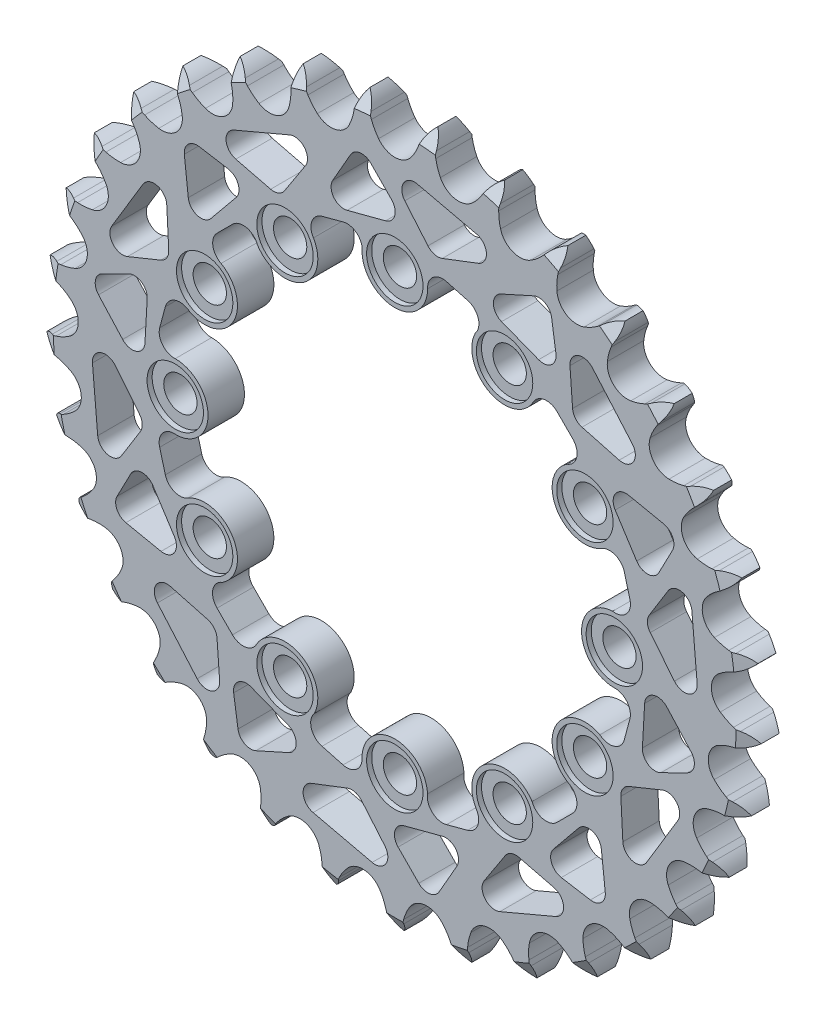
SolidWorks part; units mm, degrees
material "7075-T6 (SN)"
ref_plane "Front Plane" through (0, 0, 0) normal (0, 0, 1) x (1, 0, 0)
ref_plane "Top Plane" through (0, 0, 0) normal (0, 1, 0) x (1, 0, 0)
ref_plane "Right Plane" through (0, 0, 0) normal (1, 0, 0) x (0, 0, -1)
sketch "Work Sketch" plane through (0, 0, 0) normal (0, 0, 1) x (1, 0, 0)
  line L0 (0, 0) -> (0, 160.4542) construction
  line L1 (-112.0919, 66.8027) -> (87.2579, 66.8027) construction
  line L2 (5.0834, 120.8822) -> (5.0834, 112.9699) construction
  line L3 (-12.8497, 70.6081) -> (16.7256, 70.6081) construction
  line L4 (5.0834, 70.6081) -> (-6.0658, 62.2619) construction
  line L5 (5.0834, 70.6081) -> (-4.6352, 66.9715) construction
  line L6 (-4.6352, 66.9715) -> (-6.998, 73.2861)
  line L7 (-11.5114, 65.7464) -> (-7.1525, 65.7464) construction
  line L8 (-11.0622, 124.7602) -> (-11.0622, 110.2345) construction
  line L9 (0, 0) -> (-4.0639, 42.5596) construction
  circle A0 centre (0, 0) radius 66.8027
  circle A1 centre (0, 66.8027) radius 4.0088
  arc A2 (-4.6352, 66.9715) -> (-3.2092, 64.4003) centre (5.0609, 70.6677) ccw
  circle A3 centre (-11.0622, 65.7464) radius 6.4488
  point P23 (-3.2092, 64.4003)
  dimension "D1" = 133.6054
  dimension "D8" = 10.3767
  dimension "D2" = 8.0177
  dimension "D3" = 5.0834
  dimension "D4" = 3.8054
  dimension "D5" = 36.818
  dimension "D6" = 16.303
  dimension "D7" = 10.3767
  dimension "D9" = 1.0563
  dimension "D10" = 11.0622
  dimension "D11" = 5.455
sketch "Teeth Sketch" plane through (0, 0, 0) normal (0, 0, 1) x (1, 0, 0)
  line L0 (5.0224, 68.0064) -> (4.6352, 66.9715)
  line L1 (-8.8439, 92.6176) -> (-5.6513, 59.1829) construction
  line L2 (0, 0) -> (-12.8498, 132.1321) construction
  line L3 (7.9387, 67.7279) -> (8.123, 66.6385)
  line L4 (19011.2087, -199094.3845) -> (-19015.2726, 199136.9441) construction
  line L5 (0, 146.3285) -> (0, 56.9858) construction
  line L6 (17.8019, 65.8269) -> (17.2258, 64.8841)
  line L7 (0, -200000) -> (0, 200160.4542) construction
  line L8 (20.6128, 65.0016) -> (20.5877, 63.897)
  line L9 (-4.6352, 66.9715) -> (-6.998, 73.2861) construction
  line L10 (43.2949, 52.6844) -> (42.861, 51.6682)
  line L11 (-5.0224, 68.0064) -> (-4.6352, 66.9715)
  line L12 (29.938, 61.2683) -> (29.1939, 60.4515)
  line L13 (32.5419, 59.9259) -> (32.3082, 58.846)
  line L14 (40.9921, 54.4953) -> (40.1069, 53.8341)
  line L15 (50.5647, 45.7527) -> (49.5703, 45.271)
  line L16 (52.4831, 43.5387) -> (51.8648, 42.623)
  line L17 (58.3096, 35.3565) -> (57.2421, 35.0716)
  line L18 (59.7744, 32.8194) -> (58.9939, 32.0373)
  line L19 (63.9472, 23.6824) -> (62.845, 23.6047)
  line L20 (64.9053, 20.9139) -> (63.9909, 20.2936)
  line L21 (67.2735, 11.1523) -> (66.1765, 11.2846)
  line L22 (67.6904, 8.2526) -> (66.6751, 7.8165)
  line L23 (68.1683, -1.7808) -> (67.1162, -1.4433)
  line L24 (68.0289, -4.7071) -> (66.9495, -4.9431)
  line L25 (66.5994, -14.6496) -> (65.6302, -14.119)
  line L26 (65.9088, -17.4966) -> (64.8042, -17.524)
  line L27 (62.6234, -26.9889) -> (61.7722, -26.2845)
  line L28 (61.4065, -29.6537) -> (60.3166, -29.4716)
  line L29 (56.3841, -38.3527) -> (55.6815, -37.4999)
  line L30 (54.6848, -40.739) -> (53.6491, -40.354)
  line L31 (48.1068, -48.3304) -> (47.5783, -47.3601)
  line L32 (45.9866, -50.352) -> (45.0425, -49.7779)
  line L33 (38.0909, -56.5613) -> (37.7556, -55.5085)
  line L34 (35.6264, -58.1451) -> (34.808, -57.4027)
  line L35 (26.6983, -62.7479) -> (26.5682, -61.6506)
  line L36 (23.9786, -63.8367) -> (23.3155, -62.9529)
  line L37 (14.3407, -66.6666) -> (14.4207, -65.5646)
  line L38 (11.4641, -67.221) -> (10.9802, -66.2277)
  line L39 (1.4648, -68.1759) -> (1.7519, -67.1089)
  line L40 (-1.4648, -68.1759) -> (-1.7519, -67.1089)
  line L41 (-11.4641, -67.221) -> (-10.9802, -66.2277)
  line L42 (-14.3407, -66.6666) -> (-14.4207, -65.5646)
  line L43 (-23.9786, -63.8367) -> (-23.3155, -62.9529)
  line L44 (-26.6983, -62.7479) -> (-26.5682, -61.6506)
  line L45 (-35.6264, -58.1451) -> (-34.808, -57.4027)
  line L46 (-38.0909, -56.5613) -> (-37.7556, -55.5085)
  line L47 (-45.9866, -50.352) -> (-45.0425, -49.7779)
  line L48 (-48.1068, -48.3304) -> (-47.5783, -47.3601)
  line L49 (-54.6848, -40.739) -> (-53.6491, -40.354)
  line L50 (-56.3841, -38.3527) -> (-55.6815, -37.4999)
  line L51 (-61.4065, -29.6537) -> (-60.3166, -29.4716)
  line L52 (-62.6234, -26.9889) -> (-61.7722, -26.2845)
  line L53 (-65.9088, -17.4966) -> (-64.8042, -17.524)
  line L54 (-66.5994, -14.6496) -> (-65.6302, -14.119)
  line L55 (-68.0289, -4.7071) -> (-66.9495, -4.9431)
  line L56 (-68.1683, -1.7808) -> (-67.1162, -1.4433)
  line L57 (-67.6904, 8.2526) -> (-66.6751, 7.8165)
  line L58 (-67.2735, 11.1523) -> (-66.1765, 11.2846)
  line L59 (-64.9053, 20.9139) -> (-63.9909, 20.2936)
  line L60 (-63.9472, 23.6824) -> (-62.845, 23.6047)
  line L61 (-59.7744, 32.8194) -> (-58.9939, 32.0373)
  line L62 (-58.3096, 35.3565) -> (-57.2421, 35.0716)
  line L63 (-52.4831, 43.5387) -> (-51.8648, 42.623)
  line L64 (-50.5647, 45.7527) -> (-49.5703, 45.271)
  line L65 (-43.2949, 52.6844) -> (-42.861, 51.6682)
  line L66 (-40.9921, 54.4953) -> (-40.1069, 53.8341)
  line L67 (-32.5419, 59.9259) -> (-32.3082, 58.846)
  line L68 (-29.938, 61.2683) -> (-29.1939, 60.4515)
  line L69 (-20.6128, 65.0016) -> (-20.5877, 63.897)
  line L70 (-17.8019, 65.8269) -> (-17.2258, 64.8841)
  line L71 (-7.9387, 67.7279) -> (-8.123, 66.6385)
  arc A0 (-6.8704, 70.647) -> (-5.0224, 68.0064) centre (-11.0622, 65.7464) cw
  circle A1 centre (-11.0622, 65.7464) radius 6.4488 construction
  arc A2 (-3.2092, 64.4003) -> (-4.6352, 66.9715) centre (5.0609, 70.6677) cw
  arc A3 (-4.6352, 66.9715) -> (-3.2092, 64.4003) centre (5.0609, 70.6677) ccw construction
  circle A4 centre (0, 66.8027) radius 4.0088 construction
  arc A5 (-3.2092, 64.4003) -> (3.2092, 64.4003) centre (0, 66.8027) ccw
  arc A6 (3.2092, 64.4003) -> (4.6352, 66.9715) centre (-5.0609, 70.6677) ccw
  arc A7 (6.8704, 70.647) -> (5.0224, 68.0064) centre (11.0622, 65.7464) ccw
  arc A8 (6.6238, 70.6705) -> (7.9387, 67.7279) centre (1.5803, 66.6518) cw
  arc A9 (9.0366, 63.8438) -> (8.123, 66.6385) centre (18.3434, 68.4328) cw
  arc A10 (9.0366, 63.8438) -> (15.3391, 62.6291) centre (12.6425, 65.5955) ccw
  arc A11 (15.3391, 62.6291) -> (17.2258, 64.8841) centre (8.4044, 70.3484) ccw
  arc A12 (20.1163, 68.0701) -> (17.8019, 65.8269) centre (23.3049, 62.4647) ccw
  arc A13 (19.8786, 68.1399) -> (20.6128, 65.0016) centre (14.1657, 65.1482) cw
  arc A14 (20.9558, 60.9799) -> (20.5877, 63.897) centre (30.9629, 63.7246) cw
  arc A15 (20.9558, 60.9799) -> (26.9145, 58.5944) centre (24.8281, 62.0175) ccw
  arc A16 (26.9145, 58.5944) -> (29.1939, 60.4515) centre (21.5661, 67.4865) ccw
  arc A17 (32.6351, 63.0329) -> (29.938, 61.2683) centre (34.7052, 56.9254) ccw
  arc A18 (32.4149, 63.1465) -> (32.5419, 59.9259) centre (26.2391, 61.29) cw
  arc A19 (32.1176, 55.912) -> (32.3082, 58.846) centre (42.4634, 56.7133) cw
  arc A20 (32.1176, 55.912) -> (37.5172, 52.4419) centre (36.1163, 56.198) ccw
  arc A21 (37.5172, 52.4419) -> (40.1069, 53.8341) centre (33.9483, 62.1856) ccw
  arc A22 (43.9744, 55.7176) -> (40.9921, 54.4953) centre (44.8513, 49.3287) ccw
  arc A23 (43.7796, 55.8708) -> (43.2949, 52.6844) centre (37.3641, 55.2167) cw
  arc A24 (42.1187, 48.8233) -> (42.861, 51.6682) centre (52.429, 47.6521) cw
  arc A25 (42.1187, 48.8233) -> (46.7639, 44.3941) centre (46.0991, 48.3474) ccw
  arc A26 (46.7639, 44.3941) -> (49.5703, 45.271) centre (45.1035, 54.637) ccw
  arc A27 (53.7244, 46.3885) -> (50.5647, 45.7527) centre (53.3763, 39.9491) ccw
  arc A28 (53.5621, 46.5757) -> (52.4831, 43.5387) centre (47.1387, 47.1476) cw
  arc A29 (50.5974, 39.97) -> (51.8648, 42.623) centre (60.4998, 36.8687) cw
  arc A30 (50.5974, 39.97) -> (54.3205, 34.7417) centre (54.4159, 38.7494) ccw
  arc A31 (54.3205, 34.7417) -> (57.2421, 35.0716) centre (54.6285, 45.1138) ccw
  arc A32 (61.5326, 35.3828) -> (58.3096, 35.3565) centre (59.9721, 29.1257) ccw
  arc A33 (61.4087, 35.5974) -> (59.7744, 32.8194) centre (55.2096, 37.3746) cw
  arc A34 (57.2474, 29.6721) -> (58.9939, 32.0373) centre (66.384, 24.7528) cw
  arc A35 (57.2474, 29.6721) -> (59.9137, 23.8336) centre (60.7659, 27.7508) ccw
  arc A36 (59.9137, 23.8336) -> (62.845, 23.6047) centre (62.1792, 33.96) ccw
  arc A37 (67.1168, 23.0983) -> (63.9472, 23.6824) centre (64.4004, 17.2495) ccw
  arc A38 (67.0358, 23.3324) -> (64.9053, 20.9139) centre (61.2851, 26.2507) cw
  arc A39 (61.8283, 18.3017) -> (63.9909, 20.2936) centre (69.8688, 11.7422) cw
  arc A40 (61.8283, 18.3017) -> (63.3416, 12.0642) centre (64.9196, 15.7493) ccw
  arc A41 (63.3416, 12.0642) -> (66.1765, 11.2846) centre (67.4825, 21.5788) ccw
  arc A42 (70.2753, 9.9789) -> (67.2735, 11.1523) centre (66.5011, 4.7499) ccw
  arc A43 (70.2401, 10.2242) -> (67.6904, 8.2526) centre (65.1456, 14.178) cw
  arc A44 (64.1746, 6.2699) -> (66.6751, 7.8165) centre (70.8284, -1.6927) cw
  arc A45 (64.1746, 6.2699) -> (64.48, -0.1413) centre (66.727, 3.1786) ccw
  arc A46 (64.48, -0.1413) -> (67.1162, -1.4433) centre (70.3468, 8.4177) ccw
  arc A47 (70.8939, -3.5011) -> (68.1683, -1.7808) centre (66.1983, -7.9213) ccw
  arc A48 (70.9057, -3.2536) -> (68.0289, -4.7071) centre (66.6515, 1.5929) cw
  arc A49 (64.2015, -5.9885) -> (66.9495, -4.9431) centre (69.2281, -15.0665) cw
  arc A50 (64.2015, -5.9885) -> (63.2881, -12.3417) centre (66.1227, -9.507) ccw
  arc A51 (63.2881, -12.3417) -> (65.6302, -14.119) centre (70.6686, -5.0476) ccw
  arc A52 (68.9501, -16.8546) -> (66.5994, -14.6496) centre (63.5029, -20.3063) ccw
  arc A53 (69.0085, -16.6138) -> (65.9088, -17.4966) centre (65.7485, -11.0498) cw
  arc A54 (61.908, -18.0305) -> (64.8042, -17.524) centre (65.1257, -27.8957) cw
  arc A55 (61.908, -18.0305) -> (59.8087, -24.096) centre (63.1286, -21.849) ccw
  arc A56 (59.8087, -24.096) -> (61.7722, -26.2845) centre (68.4363, -18.3305) ccw
  arc A57 (64.5144, -29.5989) -> (62.6234, -26.9889) centre (58.5123, -31.9573) ccw
  arc A58 (64.6173, -29.3735) -> (61.4065, -29.6537) centre (62.4691, -23.2931) cw
  arc A59 (57.3769, -29.4209) -> (60.3166, -29.4716) centre (58.6695, -39.7167) cw
  arc A60 (57.3769, -29.4209) -> (54.1677, -34.9794) centre (57.8528, -33.4013) ccw
  arc A61 (54.1677, -34.9794) -> (55.6815, -37.4999) centre (63.7305, -30.9509) ccw
  arc A62 (57.7469, -41.2734) -> (56.3841, -38.3527) centre (51.4069, -42.4533) ccw
  arc A63 (57.8906, -41.0716) -> (54.6848, -40.739) centre (56.932, -34.6945) cw
  arc A64 (50.7721, -39.7478) -> (53.6491, -40.354) centre (50.0928, -50.1023) cw
  arc A65 (50.7721, -39.7478) -> (46.5689, -44.5986) centre (50.4861, -43.7465) ccw
  arc A66 (46.5689, -44.5986) -> (47.5783, -47.3601) centre (56.7213, -42.4527) ccw
  arc A67 (48.8923, -51.4562) -> (48.1068, -48.3304) centre (42.4436, -51.415) ccw
  arc A68 (49.0716, -51.2853) -> (45.9866, -50.352) centre (49.3372, -44.842) cw
  arc A69 (42.3322, -48.6382) -> (45.0425, -49.7779) centre (39.7057, -58.677) cw
  arc A70 (42.3322, -48.6382) -> (37.287, -52.6059) centre (41.2947, -52.5105) ccw
  arc A71 (37.287, -52.6059) -> (37.7556, -55.5085) centre (47.662, -52.4201) ccw
  arc A72 (38.2706, -59.7793) -> (38.0909, -56.5613) centre (31.9463, -58.5183) ccw
  arc A73 (38.479, -59.6453) -> (35.6264, -58.1451) centre (39.9592, -53.3687) cw
  arc A74 (32.3624, -55.7707) -> (34.808, -57.4027) centre (27.8834, -65.131) cw
  arc A75 (32.3624, -55.7707) -> (26.6574, -58.7118) centre (30.6108, -59.3766) ccw
  arc A76 (26.6574, -58.7118) -> (26.5682, -61.6506) centre (36.8801, -60.4929) ccw
  arc A77 (26.2657, -65.9417) -> (26.6983, -62.7479) centre (20.2943, -63.5067) ccw
  arc A78 (26.4957, -65.8497) -> (23.9786, -63.8367) centre (29.137, -59.9666) cw
  arc A79 (21.2229, -60.8875) -> (23.3155, -62.9529) centre (15.0534, -69.2309) cw
  arc A80 (21.2229, -60.8875) -> (15.0644, -62.6958) centre (18.8205, -64.0967) ccw
  arc A81 (15.0644, -62.6958) -> (14.4207, -65.5646) centre (24.7653, -66.3793) ccw
  arc A82 (13.3114, -69.7209) -> (14.3407, -66.6666) centre (7.9088, -66.1998) ccw
  arc A83 (13.5547, -69.674) -> (11.4641, -67.221) centre (17.2617, -64.3972) cw
  arc A84 (9.3163, -63.8036) -> (10.9802, -66.2277) centre (1.6794, -70.8287) cw
  arc A85 (9.3163, -63.8036) -> (2.9269, -64.4137) centre (6.35, -66.5002) ccw
  arc A86 (2.9269, -64.4137) -> (1.7519, -67.1089) centre (11.7554, -69.8666) ccw
  arc A87 (-0.1239, -70.9802) -> (1.4648, -68.1759) centre (-4.7625, -66.5002) ccw
  arc A88 (0.1239, -70.9802) -> (-1.4648, -68.1759) centre (4.7625, -66.5002) cw
  arc A89 (-2.9269, -64.4137) -> (-1.7519, -67.1089) centre (-11.7554, -69.8666) cw
  arc A90 (-2.9269, -64.4137) -> (-9.3163, -63.8036) centre (-6.35, -66.5002) ccw
  arc A91 (-9.3163, -63.8036) -> (-10.9802, -66.2277) centre (-1.6794, -70.8287) ccw
  arc A92 (-13.5547, -69.674) -> (-11.4641, -67.221) centre (-17.2617, -64.3972) ccw
  arc A93 (-13.3114, -69.7209) -> (-14.3407, -66.6666) centre (-7.9088, -66.1998) cw
  arc A94 (-15.0644, -62.6958) -> (-14.4207, -65.5646) centre (-24.7653, -66.3793) cw
  arc A95 (-15.0644, -62.6958) -> (-21.2229, -60.8875) centre (-18.8205, -64.0967) ccw
  arc A96 (-21.2229, -60.8875) -> (-23.3155, -62.9529) centre (-15.0534, -69.2309) ccw
  arc A97 (-26.4957, -65.8497) -> (-23.9786, -63.8367) centre (-29.137, -59.9666) ccw
  arc A98 (-26.2657, -65.9417) -> (-26.6983, -62.7479) centre (-20.2943, -63.5067) cw
  arc A99 (-26.6574, -58.7118) -> (-26.5682, -61.6506) centre (-36.8801, -60.4929) cw
  arc A100 (-26.6574, -58.7118) -> (-32.3624, -55.7707) centre (-30.6108, -59.3766) ccw
  arc A101 (-32.3624, -55.7707) -> (-34.808, -57.4027) centre (-27.8834, -65.131) ccw
  arc A102 (-38.479, -59.6453) -> (-35.6264, -58.1451) centre (-39.9592, -53.3687) ccw
  arc A103 (-38.2706, -59.7793) -> (-38.0909, -56.5613) centre (-31.9463, -58.5183) cw
  arc A104 (-37.287, -52.6059) -> (-37.7556, -55.5085) centre (-47.662, -52.4201) cw
  arc A105 (-37.287, -52.6059) -> (-42.3322, -48.6382) centre (-41.2947, -52.5105) ccw
  arc A106 (-42.3322, -48.6382) -> (-45.0425, -49.7779) centre (-39.7057, -58.677) ccw
  arc A107 (-49.0716, -51.2853) -> (-45.9866, -50.352) centre (-49.3372, -44.842) ccw
  arc A108 (-48.8923, -51.4562) -> (-48.1068, -48.3304) centre (-42.4436, -51.415) cw
  arc A109 (-46.5689, -44.5986) -> (-47.5783, -47.3601) centre (-56.7213, -42.4527) cw
  arc A110 (-46.5689, -44.5986) -> (-50.7721, -39.7478) centre (-50.4861, -43.7465) ccw
  arc A111 (-50.7721, -39.7478) -> (-53.6491, -40.354) centre (-50.0928, -50.1023) ccw
  arc A112 (-57.8906, -41.0716) -> (-54.6848, -40.739) centre (-56.932, -34.6945) ccw
  arc A113 (-57.7469, -41.2734) -> (-56.3841, -38.3527) centre (-51.4069, -42.4533) cw
  arc A114 (-54.1677, -34.9794) -> (-55.6815, -37.4999) centre (-63.7305, -30.9509) cw
  arc A115 (-54.1677, -34.9794) -> (-57.3769, -29.4209) centre (-57.8528, -33.4013) ccw
  arc A116 (-57.3769, -29.4209) -> (-60.3166, -29.4716) centre (-58.6695, -39.7167) ccw
  arc A117 (-64.6173, -29.3735) -> (-61.4065, -29.6537) centre (-62.4691, -23.2931) ccw
  arc A118 (-64.5144, -29.5989) -> (-62.6234, -26.9889) centre (-58.5123, -31.9573) cw
  arc A119 (-59.8087, -24.096) -> (-61.7722, -26.2845) centre (-68.4363, -18.3305) cw
  arc A120 (-59.8087, -24.096) -> (-61.908, -18.0305) centre (-63.1286, -21.849) ccw
  arc A121 (-61.908, -18.0305) -> (-64.8042, -17.524) centre (-65.1257, -27.8957) ccw
  arc A122 (-69.0085, -16.6138) -> (-65.9088, -17.4966) centre (-65.7485, -11.0498) ccw
  arc A123 (-68.9501, -16.8546) -> (-66.5994, -14.6496) centre (-63.5029, -20.3063) cw
  arc A124 (-63.2881, -12.3417) -> (-65.6302, -14.119) centre (-70.6686, -5.0476) cw
  arc A125 (-63.2881, -12.3417) -> (-64.2015, -5.9885) centre (-66.1227, -9.507) ccw
  arc A126 (-64.2015, -5.9885) -> (-66.9495, -4.9431) centre (-69.2281, -15.0665) ccw
  arc A127 (-70.9057, -3.2536) -> (-68.0289, -4.7071) centre (-66.6515, 1.5929) ccw
  arc A128 (-70.8939, -3.5011) -> (-68.1683, -1.7808) centre (-66.1983, -7.9213) cw
  arc A129 (-64.48, -0.1413) -> (-67.1162, -1.4433) centre (-70.3468, 8.4177) cw
  arc A130 (-64.48, -0.1413) -> (-64.1746, 6.2699) centre (-66.727, 3.1786) ccw
  arc A131 (-64.1746, 6.2699) -> (-66.6751, 7.8165) centre (-70.8284, -1.6927) ccw
  arc A132 (-70.2401, 10.2242) -> (-67.6904, 8.2526) centre (-65.1456, 14.178) ccw
  arc A133 (-70.2753, 9.9789) -> (-67.2735, 11.1523) centre (-66.5011, 4.7499) cw
  arc A134 (-63.3416, 12.0642) -> (-66.1765, 11.2846) centre (-67.4825, 21.5788) cw
  arc A135 (-63.3416, 12.0642) -> (-61.8283, 18.3017) centre (-64.9196, 15.7493) ccw
  arc A136 (-61.8283, 18.3017) -> (-63.9909, 20.2936) centre (-69.8688, 11.7422) ccw
  arc A137 (-67.0358, 23.3324) -> (-64.9053, 20.9139) centre (-61.2851, 26.2507) ccw
  arc A138 (-67.1168, 23.0983) -> (-63.9472, 23.6824) centre (-64.4004, 17.2495) cw
  arc A139 (-59.9137, 23.8336) -> (-62.845, 23.6047) centre (-62.1792, 33.96) cw
  arc A140 (-59.9137, 23.8336) -> (-57.2474, 29.6721) centre (-60.7659, 27.7508) ccw
  arc A141 (-57.2474, 29.6721) -> (-58.9939, 32.0373) centre (-66.384, 24.7528) ccw
  arc A142 (-61.4087, 35.5974) -> (-59.7744, 32.8194) centre (-55.2096, 37.3746) ccw
  arc A143 (-61.5326, 35.3828) -> (-58.3096, 35.3565) centre (-59.9721, 29.1257) cw
  arc A144 (-54.3205, 34.7417) -> (-57.2421, 35.0716) centre (-54.6285, 45.1138) cw
  arc A145 (-54.3205, 34.7417) -> (-50.5974, 39.97) centre (-54.4159, 38.7494) ccw
  arc A146 (-50.5974, 39.97) -> (-51.8648, 42.623) centre (-60.4998, 36.8687) ccw
  arc A147 (-53.5621, 46.5757) -> (-52.4831, 43.5387) centre (-47.1387, 47.1476) ccw
  arc A148 (-53.7244, 46.3885) -> (-50.5647, 45.7527) centre (-53.3763, 39.9491) cw
  arc A149 (-46.7639, 44.3941) -> (-49.5703, 45.271) centre (-45.1035, 54.637) cw
  arc A150 (-46.7639, 44.3941) -> (-42.1187, 48.8233) centre (-46.0991, 48.3474) ccw
  arc A151 (-42.1187, 48.8233) -> (-42.861, 51.6682) centre (-52.429, 47.6521) ccw
  arc A152 (-43.7796, 55.8708) -> (-43.2949, 52.6844) centre (-37.3641, 55.2167) ccw
  arc A153 (-43.9744, 55.7176) -> (-40.9921, 54.4953) centre (-44.8513, 49.3287) cw
  arc A154 (-37.5172, 52.4419) -> (-40.1069, 53.8341) centre (-33.9483, 62.1856) cw
  arc A155 (-37.5172, 52.4419) -> (-32.1176, 55.912) centre (-36.1163, 56.198) ccw
  arc A156 (-32.1176, 55.912) -> (-32.3082, 58.846) centre (-42.4634, 56.7133) ccw
  arc A157 (-32.4149, 63.1465) -> (-32.5419, 59.9259) centre (-26.2391, 61.29) ccw
  arc A158 (-32.6351, 63.0329) -> (-29.938, 61.2683) centre (-34.7052, 56.9254) cw
  arc A159 (-26.9145, 58.5944) -> (-29.1939, 60.4515) centre (-21.5661, 67.4865) cw
  arc A160 (-26.9145, 58.5944) -> (-20.9558, 60.9799) centre (-24.8281, 62.0175) ccw
  arc A161 (-20.9558, 60.9799) -> (-20.5877, 63.897) centre (-30.9629, 63.7246) ccw
  arc A162 (-19.8786, 68.1399) -> (-20.6128, 65.0016) centre (-14.1657, 65.1482) ccw
  arc A163 (-20.1163, 68.0701) -> (-17.8019, 65.8269) centre (-23.3049, 62.4647) cw
  arc A164 (-15.3391, 62.6291) -> (-17.2258, 64.8841) centre (-8.4044, 70.3484) cw
  arc A165 (-15.3391, 62.6291) -> (-9.0366, 63.8438) centre (-12.6425, 65.5955) ccw
  arc A166 (-9.0366, 63.8438) -> (-8.123, 66.6385) centre (-18.3434, 68.4328) ccw
  arc A167 (-6.6238, 70.6705) -> (-7.9387, 67.7279) centre (-1.5803, 66.6518) ccw
  point P77 (0, 0)
  dimension "D1" = 5.455
  dimension "D2" = 5.555
  dimension "D3" = 33
extrude "Extrusion" add sketch "Teeth Sketch" along normal blind 7.2136 contours A0 region at (0, 0, 0)
ref_axis "Axis2" through (0, 0, 38.9715) along (0, 0, -1)
hole_wizard "M6 Clearance Hole1" positions "Sketch6" profile "Sketch7" hole size "M6" standard "ANSI Metric"
sketch "Sketch6" plane through (0, 0, 0) normal (0, 0, -1) x (-1, 0, 0)
  circle A0 centre (0, 0) radius 43.5
  point P0 (0, 43.5)
  dimension "D1" = 87
sketch "Sketch7" plane through (0, 43.5, 0) normal (1, 0, 0) x (0, 1, 0)
  line L0 (0, 0) -> (0, 19.2548)
  line L1 (0, 19.2548) -> (3.3, 17.272)
  line L2 (3.3, 17.272) -> (3.3, 0)
  line L5 (3.3, 0) -> (0, 0)
  line L10 (0, 19.2548) -> (-3.3, 17.272) construction
  line L11 (0, -6.35) -> (0, 107.95) construction
  dimension "Hole Dia." = 6.6
  dimension "Hole Depth" = 17.272
  dimension "Drill Angle" = 118
pattern_circular "CirPattern1" count 12 over 360 about axis through (0, 0, 38.9715) along (0, 0, -1) of "M6 Clearance Hole1"
sketch "Sketch8" plane through (0, 0, 0) normal (0, 0, -1) x (-1, 0, 0)
  circle A0 centre (0, 0) radius 37
  dimension "D1" = 74
extrude "Cut-Extrude1" cut sketch "Sketch8" against normal through all both and the other way through all
ref_plane "Sprocket Center Plane" through (0, 0, 3.6068) normal (0, 0, 1) x (1, 0, 0)
sketch "Pitch Circle" plane through (0, 0, 3.6068) normal (0, 0, -1) x (-1, 0, 0)
  circle A0 centre (0, 0) radius 66.8027 construction
  dimension "D1" = 133.6054
ref_plane "Center Plane" through (0, 0, 3.6068) normal (0, 0, 1) x (1, 0, 0)
ref_axis "Axis1" through (0, 0, 7.2136) along (0, 0, -1)
sketch "Sketch5" plane through (0, 0, 0) normal (1, 0, 0) x (0, 0, -1)
  line L0 (-1.8288, -70.8482) -> (-5.3848, -70.8482)
  line L1 (-7.2136, -51.2753) -> (0, -51.2753) construction
  line L2 (-5.3848, -70.8482) -> (-5.3848, -67.6547)
  line L3 (-5.3848, -67.6547) -> (-7.2136, -67.6547)
  line L4 (-7.2136, -67.6547) -> (-5.3848, -70.8482)
  line L5 (-7.2136, -67.6547) -> (-7.2136, -70.8482)
  line L6 (-7.2136, -70.8482) -> (-5.3848, -70.8482)
  line L8 (-7.2136, -70.8482) -> (0, -70.8482) construction
  dimension "D1" = 3.556
  dimension "D2" = 3.1936
  dimension "D3" = 1.8288
revolve "Cut-Revolve1" cut sketch "Sketch5" angle 360 about axis through (0, 0, 7.2136) along (0, 0, -1) region at (0, -69.7837, 6.604)
mirror "Mirror1" about plane through (0, 0, 3.6068) normal (0, 0, 1) of "Cut-Revolve1"
sketch "Sketch10" plane through (0, 0, 0) normal (0, 0, 1) x (1, 0, 0)
  circle A0 centre (-43.5, 0) radius 5.588
  dimension "D1" = 11.176
extrude "Cut-Extrude2" cut sketch "Sketch10" against normal blind 1.016 from surface starting at face at (-37, 0, 7.2136)
pattern_circular "CirPattern2" count 12 over 360 about axis through (0, 0, 38.9715) along (0, 0, -1) of "Cut-Extrude2"
ref_plane "Half Plane" through (0, 0, 3.6068) normal (0, 0, 1) x (1, 0, 0)
sketch "Motor Shaft Sprocket Dimensions" plane through (0, 0, 3.6068) normal (0, 0, 1) x (1, 0, 0)
  line L0 (0, 0) -> (-177.8, 0)
  line L1 (-177.8, 0) -> (-177.8, 23.6982)
  line L2 (-180.2273, 51.0991) -> (-5.8945, 66.5421)
  line L3 (-187.3193, -2.1104) -> (-23.1174, -62.6753)
  line L4 (-5.8945, 66.5421) -> (0, 0)
  line L5 (0, 0) -> (-23.1174, -62.6753)
  circle A0 centre (-177.8, 23.6982) radius 27.5082
  circle A1 centre (0, 0) radius 66.8027 construction
  dimension "D3" = 55.0164
  dimension "D1" = 177.8
  dimension "D2" = 23.6982
  dimension "D4" = 205.308
sketch "Sketch11" plane through (0, 0, 0) normal (0, 0, 1) x (1, 0, 0)
  line L0 (-167.2094, -55.7997) -> (-36.0913, 46.3337)
  line L1 (-145.9214, -98.8914) -> (14.8674, -56.8186)
  circle A2 centre (-152.1323, -75.1555) radius 24.535
  circle A3 centre (0, 0) radius 58.7316
  dimension "D2" = 117.4631
  dimension "D3" = 49.07
  dimension "D1" = 169.6838
sketch "Sketch12" plane through (0, 0, 7.2136) normal (0, 0, 1) x (1, 0, 0)
  line L0 (0, 43.5) -> (21.75, 37.6721) construction
  line L1 (9.5763, 35.7393) -> (13.8192, 51.5738) construction
  line L2 (10.2476, 46.5861) -> (14.4184, 45.4686) construction
  line L6 (9.4955, 43.681) -> (13.6664, 42.5634) construction
  line L7 (10.2476, 46.5861) -> (14.4184, 45.4686)
  circle A0 centre (21.75, 37.6721) radius 5.588 construction
  circle A1 centre (0, 43.5) radius 5.588 construction
  circle A2 centre (21.75, 37.6721) radius 5.588 construction
  circle A3 centre (0, 43.5) radius 5.588 construction
  circle A4 centre (0, 43.5) radius 6.5 construction
  circle A5 centre (21.75, 37.6721) radius 6.5 construction
  circle A6 centre (0, 0) radius 37 construction
  arc A7 (0, 37) -> (18.5, 32.0429) centre (0, 0) cw
  circle A8 centre (0, 0) radius 37 construction
  arc A9 (10.2476, 46.5861) -> (6.5, 43.5) centre (9.4955, 43.681) ccw
  arc A10 (14.4184, 45.4686) -> (15.9628, 40.6315) centre (13.6664, 42.5634) cw
  arc A20 (0, 37) -> (6.5, 43.5) centre (0, 43.5) ccw
  arc A21 (15.9628, 40.6315) -> (18.5, 32.0429) centre (21.75, 37.6721) ccw
  dimension "D1" = 42.0178
  dimension "D2" = 5.6332
  dimension "D6" = 4.318
  dimension "D7" = 3.0009
extrude "Cut-Extrude3" cut sketch "Sketch12" against normal through all contours A21 A7 A20 A9 L7 A10
pattern_circular "CirPattern3" count 12 over 360 about axis through (0, 0, 7.2136) along (0, 0, -1) of "Cut-Extrude3" reverse direction yes
sketch "Sketch13" plane through (0, 0, 7.2136) normal (0, 0, 1) x (1, 0, 0)
  line L0 (-12.295, 52.6993) -> (-8.767, 58.8746)
  line L1 (-4.7487, 59.3936) -> (-0.6568, 55.2241)
  line L2 (-1.8231, 50.9886) -> (-9.4431, 48.983)
  line L3 (1.9797, 56.3209) -> (6.5673, 50.8863)
  line L4 (9.4175, 50.1531) -> (16.5325, 52.881)
  line L5 (16.1956, 57.7273) -> (4.493, 60.434)
  arc A0 (-4.7487, 59.3936) -> (-8.767, 58.8746) centre (-6.5615, 57.6145) ccw
  arc A1 (-9.4431, 48.983) -> (-12.295, 52.6993) centre (-10.0896, 51.4393) cw
  arc A2 (-1.8231, 50.9886) -> (-0.6568, 55.2241) centre (-2.4696, 53.445) ccw
  arc A3 (9.4175, 50.1531) -> (6.5673, 50.8863) centre (8.5082, 52.5247) cw
  arc A4 (4.493, 60.434) -> (1.9797, 56.3209) centre (3.9206, 57.9593) ccw
  arc A5 (16.5325, 52.881) -> (16.1956, 57.7273) centre (15.6232, 55.2526) ccw
  circle A6 centre (0, 0) radius 43.5 construction
  dimension "D13" = 2.54
  dimension "D15" = 7.62
  dimension "D16" = 2.54
  dimension "D1" = 51.4393
  dimension "D2" = 53.445
  dimension "D3" = 57.6145
  dimension "D4" = 10.0896
  dimension "D5" = 2.4696
  dimension "D6" = 6.5615
  dimension "D7" = 3.9206
  dimension "D8" = 8.5082
  dimension "D9" = 15.6232
  dimension "D10" = 52.5247
  dimension "D11" = 55.2526
  dimension "D12" = 57.9593
  dimension "D14" = 7.112
  dimension "D17" = 7.112
extrude "Cut-Extrude4" cut sketch "Sketch13" against normal through all
pattern_circular "CirPattern5" count 10 over 360 about axis through (0, 0, 38.9715) along (0, 0, -1) of "Cut-Extrude4"
equation "\"P\"= 0.500'//Chain Pitch"
equation "\"N\"= 33'//Number of Teeth"
equation "\"Dr\"= 5 / 16'//Roller Diameter"
equation "\"Ds\"= 1.0005 * \"Dr\" + 0.003'Seating Curve DIameter"
equation "\"R\"= \"Ds\" / 2"
equation "\"A\"= 35 + 60 / \"N\""
equation "\"B\"= 18 - 56 / \"N\""
equation "\"ac\"= 0.8 * \"Dr\""
equation "\"M\"= 0.8 * \"Dr\" * cos ( 35 + 60 / \"N\" )"
equation "\"T\"= 0.8 * \"Dr\" * sin ( 35 + 60 / \"N\" )"
equation "\"E\"= 1.3025 * \"Dr\" + 0.0015"
equation "\"Chordal Length of Arc xy\"= ( 2.605 * \"Dr\" + 0.003 ) * sin ( 9 - 28 / \"N\" )"
equation "\"yz\"= \"Dr\" * ( 1.4 * sin ( 17 - 64 / \"N\" ) - 0.8 * sin ( 18 - 56 / \"N\" ) )"
equation "\"ab\"= 1.4 * \"Dr\""
equation "\"W\"= 1.4 * \"Dr\" * cos ( 180 / \"N\" )"
equation "\"V\"= 1.4 * \"Dr\" * sin ( 180 / \"N\" )"
equation "\"F\"= \"Dr\" * ( 0.8 * cos ( 18 - 56 / \"N\" ) + 1.4 * cos ( 17 - 64 / \"N\" ) - 1.3025 )"
equation "\"H\"= sqr ( \"F\" ^ 2 - ( 1.4 * \"Dr\" - \"P\" / 2 ) ^ 2 )"
equation "\"S\"= \"P\" / 2 * cos ( 180 / \"N\" ) + \"H\" * sin ( 180 / \"N\" )"
equation "\"PD\"= \"P\" / ( sin ( 180 / \"N\" ) )"
equation "\"D1@Work Sketch\" = \"PD\""
equation "\"D3@Work Sketch\" = \"M\""
equation "\"D4@Work Sketch\" = \"T\""
equation "\"D5@Work Sketch\" = \"A\""
equation "\"D6@Work Sketch\" = \"B\""
equation "\"D7@Work Sketch\" = \"E\""
equation "\"D8@Work Sketch\" = \"E\""
equation "\"D9@Work Sketch\" = \"V\""
equation "\"D10@Work Sketch\" = \"W\""
equation "\"D2@Work Sketch\" = \"R\" * 2"
equation "\"D11@Work Sketch\" = 180 / \"N\""
equation "\"D2@Teeth Sketch\" = 180 / \"N\" + 0.1"
equation "\"D3@Teeth Sketch\" = \"N\""
equation "\"Edge Thickness\"=0.5"
equation "\"D1@Pitch Circle\"=\"PD\""
equation "\"ST\"= 0.284'//Sprocket Thickness"
